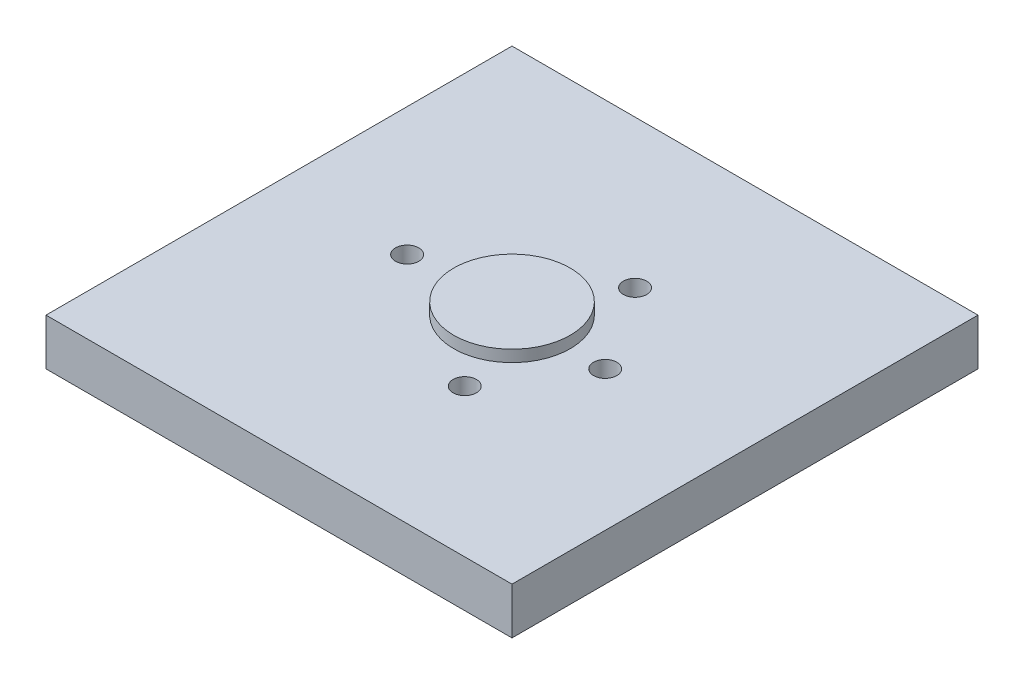
SolidWorks part; units mm, degrees
ref_plane "Front Plane" through (0, 0, 0) normal (0, 0, 1) x (1, 0, 0)
ref_plane "Top Plane" through (0, 0, 0) normal (0, 1, 0) x (1, 0, 0)
ref_plane "Right Plane" through (0, 0, 0) normal (1, 0, 0) x (0, 0, -1)
sketch "Sketch1" plane through (0, 0, 0) normal (0, 1, 0) x (1, 0, 0)
  line L1 (-63.5, 63.5) -> (63.5, 63.5)
  line L2 (-63.5, 63.5) -> (-63.5, -63.5)
  line L3 (-63.5, -63.5) -> (63.5, -63.5)
  line L4 (63.5, 63.5) -> (63.5, -63.5)
  line L5 (-63.5, 63.5) -> (63.5, -63.5) construction
  line L6 (-63.5, -63.5) -> (63.5, 63.5) construction
  point P0 (0, 0)
  dimension "D1" = 127
extrude "Boss-Extrude1" add sketch "Sketch1" along normal blind 12.7
sketch "Sketch3" plane through (0, 12.7, 0) normal (0, 1, 0) x (1, 0, 0)
  circle A0 centre (0, 0) radius 15.875
  dimension "D1" = 31.75
extrude "Boss-Extrude2" add sketch "Sketch3" along normal blind 3.175
hole_wizard "1/4 (0.25) Diameter Hole1" positions "Sketch5" profile "Sketch4" hole size "1/4" standard "ANSI Inch" end condition up to next
sketch "Sketch5" plane through (0, 12.7, 0) normal (0, 1, 0) x (1, 0, 0)
  line L0 (0, 0) -> (63.5, 0) construction
  line L1 (63.5, -63.5) -> (63.5, 63.5) construction
  line L4 (0, 0) -> (63.5, 142.6233) construction
  line L6 (0, 0) -> (63.5, -142.6233) construction
  circle A0 centre (0, 0) radius 25.4 construction
  point P0 (10.3311, 23.2041)
  point P2 (25.4, 0)
  point P4 (10.3311, -23.2041)
  dimension "D1" = 50.8
  dimension "D2" = 66
sketch "Sketch4" plane through (10.3311, 12.7, -23.2041) normal (1, 0, 0) x (0, 0, 1)
  line L0 (0, 0) -> (0, 12.7)
  line L1 (0, 12.7) -> (3.175, 12.7)
  line L2 (3.175, 12.7) -> (3.175, 0)
  line L5 (3.175, 0) -> (0, 0)
  line L11 (0, -6.35) -> (0, 107.95) construction
  dimension "Thru Hole Dia." = 6.35
  dimension "Thru Hole Depth" = 12.7
hole_wizard "1/4 (0.25) Diameter Hole2" positions "Sketch8" profile "Sketch9" hole size "1/4" standard "ANSI Inch" end condition up to next
sketch "Sketch8" plane through (0, 12.7, 0) normal (0, 1, 0) x (1, 0, 0)
  line L2 (0, 0) -> (-63.5, 0) construction
  line L3 (-63.5, 63.5) -> (-63.5, -63.5) construction
  point P0 (-28.575, 0)
  dimension "D1" = 28.575
sketch "Sketch9" plane through (-28.575, 12.7, 0) normal (1, 0, 0) x (0, 0, 1)
  line L0 (0, 0) -> (0, 12.7)
  line L1 (0, 12.7) -> (3.175, 12.7)
  line L2 (3.175, 12.7) -> (3.175, 0)
  line L5 (3.175, 0) -> (0, 0)
  line L11 (0, -6.35) -> (0, 107.95) construction
  dimension "Thru Hole Dia." = 6.35
  dimension "Thru Hole Depth" = 12.7
